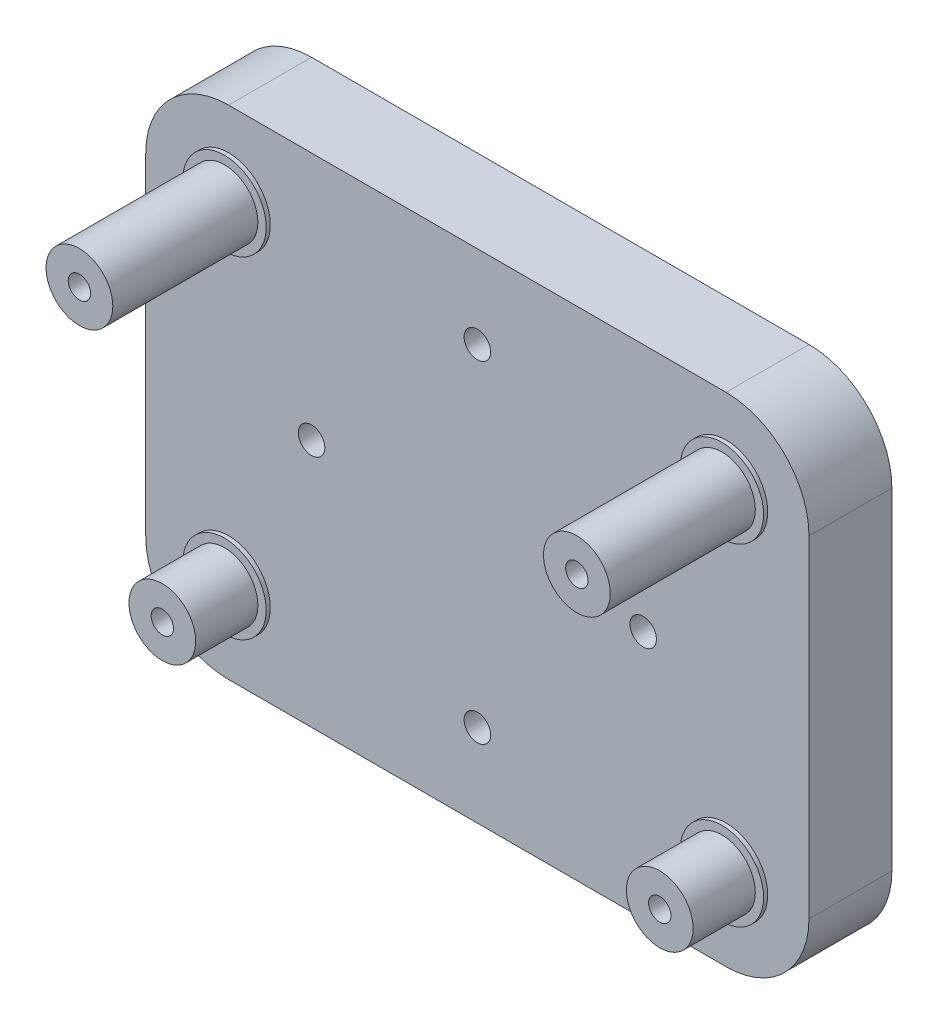
SolidWorks part; units mm, degrees
ref_plane "Front Plane" through (0, 0, 0) normal (0, 0, 1) x (1, 0, 0)
ref_plane "Top Plane" through (0, 0, 0) normal (0, 1, 0) x (1, 0, 0)
ref_plane "Right Plane" through (0, 0, 0) normal (1, 0, 0) x (0, 0, -1)
ref_axis "X" through (-88.99, 0, 0) along (1, 0, 0)
ref_axis "Y" through (0, 55, 0) along (0, -1, 0)
ref_axis "Z" through (0, 0, -88.99) along (0, 0, 1)
sketch "Sketch1" plane through (0, 0, 0) normal (0, 0, 1) x (1, 0, 0)
  line L0 (-20, 0) -> (20, 0) construction
  line L1 (-30, 20) -> (30, 20) construction
  line L2 (-30, 20) -> (-30, -20) construction
  line L3 (-30, -20) -> (30, -20) construction
  line L4 (30, 20) -> (30, -20) construction
  line L5 (-30, 20) -> (30, -20) construction
  line L6 (-30, -20) -> (30, 20) construction
  line L7 (-40, 30) -> (40, 30)
  line L8 (-40, 30) -> (-40, -30)
  line L9 (-40, -30) -> (40, -30)
  line L10 (40, 30) -> (40, -30)
  line L11 (-40, 30) -> (40, -30) construction
  line L12 (-40, -30) -> (40, 30) construction
  circle A0 centre (-30, 20) radius 4.025
  circle A1 centre (-30, -20) radius 4.025
  circle A2 centre (30, -20) radius 4.025
  circle A3 centre (30, 20) radius 4.025
  circle A4 centre (-30, 20) radius 5.025
  circle A5 centre (30, 20) radius 5.025
  circle A6 centre (30, -20) radius 5.025
  circle A7 centre (-30, -20) radius 5.025
  circle A8 centre (-30, 20) radius 1.35
  circle A9 centre (-30, -20) radius 1.35
  circle A10 centre (30, 20) radius 1.35
  circle A11 centre (30, -20) radius 1.35
  circle A12 centre (-20, 0) radius 1.6
  circle A13 centre (0, 20) radius 1.6
  circle A14 centre (20, 0) radius 1.6
  circle A15 centre (0, -20) radius 1.6
  point P0 (0, 0)
  point P10 (0, 0)
  point P31 (0, 0)
  dimension "D1" = 40
  dimension "D3" = 8.05
  dimension "D6" = 1
  dimension "D7" = 2.7
  dimension "D8" = 3.2
  dimension "D2" = 60
  dimension "D4" = 10
  dimension "D5" = 10
  dimension "D9" = 40
extrude "Boss-Extrude1" add sketch "Sketch1" against normal blind 10 contours L8 L9 L10 L7
extrude "Boss-Extrude2" add sketch "Sketch1<3>" along normal blind 8 contours A1 A9 | A2 A11 region at (-33.9112, -20, 0) region at (26.0888, -20, 0)
sketch "Sketch1<3>" plane through (0, 0, 0) normal (0, 0, 1) x (1, 0, 0) same geometry as "Sketch1"
extrude "Boss-Extrude4" add sketch "Sketch1<5>" along normal blind 18 contours A0 A8 | A3 A10 region at (-33.9112, 20, 0) region at (26.0888, 20, 0)
sketch "Sketch1<5>" plane through (0, 0, 0) normal (0, 0, 1) x (1, 0, 0) same geometry as "Sketch1"
extrude "Boss-Extrude3" add sketch "Sketch1<4>" along normal blind 0.5 contours A4 A0 | A5 A3 | A6 A2 | A7 A1 region at (-34.8829, 20, 0) region at (25.1171, 20, 0) region at (25.1171, -20, 0) region at (-34.8829, -20, 0)
sketch "Sketch1<4>" plane through (0, 0, 0) normal (0, 0, 1) x (1, 0, 0) same geometry as "Sketch1"
extrude "Cut-Extrude1" cut sketch "Sketch1<6>" against normal through all both and the other way through all contours A13 | A12 | A15 | A14 region at (-20, 0, 0) region at (0, 20, 0) region at (20, 0, 0) region at (0, -20, 0)
sketch "Sketch1<6>" plane through (0, 0, 0) normal (0, 0, 1) x (1, 0, 0) same geometry as "Sketch1"
fillet "Fillet1" radius 10 4 edges at (40, 30, -5) (40, -30, -5) (-40, -30, -5) (-40, 30, -5)
